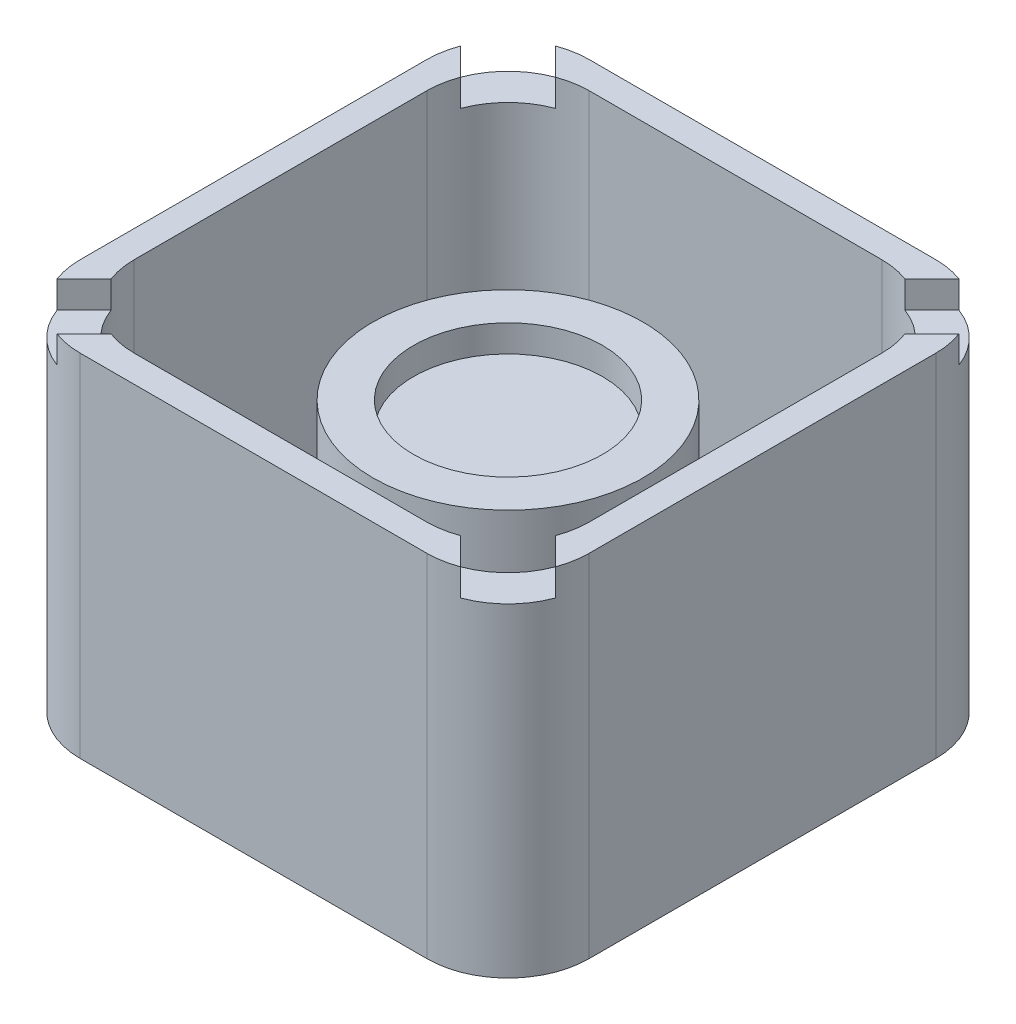
SolidWorks part; units mm, degrees
ref_plane "前视基准面" through (0, 0, 0) normal (0, 0, 1) x (1, 0, 0)
ref_plane "上视基准面" through (0, 0, 0) normal (0, 1, 0) x (1, 0, 0)
ref_plane "右视基准面" through (0, 0, 0) normal (1, 0, 0) x (0, 0, -1)
sketch "草图1" plane through (0, 0, 0) normal (0, 1, 0) x (1, 0, 0)
  line L0 (8.5413, 10.2987) -> (6.4721, 8.2295)
  line L1 (-6.42, 9.42) -> (6.42, 9.42)
  line L2 (-9.42, 6.42) -> (-9.42, -6.42)
  line L3 (-6.42, -9.42) -> (6.42, -9.42)
  line L4 (9.42, 6.42) -> (9.42, -6.42)
  line L5 (0, -9.42) -> (0, 9.42) construction
  line L6 (-9.42, 0) -> (9.42, 0) construction
  line L7 (-9.42, 9.42) -> (9.42, 9.42)
  line L8 (-9.42, 9.42) -> (-9.42, 28.26)
  line L9 (-9.42, 28.26) -> (9.42, 28.26)
  line L10 (9.42, 9.42) -> (9.42, 28.26)
  line L11 (0, 28.26) -> (0, 9.42) construction
  line L12 (-9.42, 18.84) -> (9.42, 18.84) construction
  line L13 (6.42, 12.42) -> (8.5413, 10.2987)
  line L14 (-5.42, 8.42) -> (5.42, 8.42)
  line L15 (8.42, 5.42) -> (8.42, -5.42)
  line L16 (-5.42, -8.42) -> (5.42, -8.42)
  line L17 (-8.42, 5.42) -> (-8.42, -5.42)
  line L18 (-9.42, 8.42) -> (9.42, 8.42) construction
  line L19 (-8.42, 9.42) -> (-8.42, -8.42) construction
  line L20 (8.42, 9.42) -> (8.42, -8.42) construction
  line L21 (-9.42, 9.42) -> (9.42, 9.42) construction
  line L22 (-9.42, 9.42) -> (-9.42, -9.42) construction
  line L23 (-9.42, -9.42) -> (9.42, -9.42) construction
  line L24 (-8.42, -8.42) -> (8.42, -8.42) construction
  line L25 (9.42, 9.42) -> (9.42, -9.42) construction
  line L26 (0, 0) -> (6.42, 6.42)
  line L27 (10.2987, 8.5413) -> (8.2295, 6.4721)
  line L28 (10.2987, -8.5413) -> (8.2295, -6.4721)
  line L29 (8.5413, -10.2987) -> (6.4721, -8.2295)
  line L30 (-8.5413, -10.2987) -> (-6.4721, -8.2295)
  line L31 (-10.2987, -8.5413) -> (-8.2295, -6.4721)
  line L32 (-10.2987, 8.5413) -> (-8.2295, 6.4721)
  line L33 (-8.5413, 10.2987) -> (-6.4721, 8.2295)
  circle A0 centre (6.42, 12.42) radius 3
  arc A1 (-6.42, 9.42) -> (-9.42, 6.42) centre (-6.42, 6.42) ccw
  arc A2 (-5.42, 8.42) -> (-8.42, 5.42) centre (-5.42, 5.42) ccw
  arc A3 (-6.42, -9.42) -> (-9.42, -6.42) centre (-6.42, -6.42) cw
  arc A4 (-5.42, -8.42) -> (-8.42, -5.42) centre (-5.42, -5.42) cw
  arc A5 (5.42, -8.42) -> (8.42, -5.42) centre (5.42, -5.42) ccw
  arc A6 (6.42, -9.42) -> (9.42, -6.42) centre (6.42, -6.42) ccw
  arc A7 (8.42, 5.42) -> (5.42, 8.42) centre (5.42, 5.42) ccw
  arc A8 (9.42, 6.42) -> (6.42, 9.42) centre (6.42, 6.42) ccw
  point P0 (0, 0)
  point P65 (0, 0)
  point P240 (0, 18.84)
  dimension "D4" = 6
  dimension "D6" = 3
  dimension "D1" = 16.84
  dimension "D2" = 18.84
  dimension "D3" = 18.84
  dimension "D5" = 1
  dimension "D7" = 16.84
  dimension "D8" = 4
extrude "凸台-拉伸3" add sketch "草图1" against normal blind 10 contours L31 A4 L17 A2 L32 A1 L2 A3 | A2 L33 A1 L32 | L0 A8 L1 A1 L33 A2 L14 A7 | L30 A4 L31 A3 | L3 A6 L29 A5 L16 A4 L30 A3 | L29 A6 L28 A5 | L4 A8 L27 A7 L15 A5 L28 A6 | L27 A8 L0 A7 region at (0, 0, -8.9199) region at (7.979, 0, -7.979) region at (8.9199, 0, 0) region at (-7.979, 0, -7.979) region at (-8.9199, 0, 0) region at (7.979, 0, 7.979) region at (0, 0, 8.9199) region at (-7.979, 0, 7.979)
extrude "凸台-拉伸4" add sketch "草图1<6>" against normal blind 2 from surface contours L15 A7 L14 A2 L17 A4 L16 A5 | A2 L33 A1 L32 | L31 A4 L17 A2 L32 A1 L2 A3 | L30 A4 L31 A3 | L3 A6 L29 A5 L16 A4 L30 A3 | L4 A8 L27 A7 L15 A5 L28 A6 | L29 A6 L28 A5 | L0 A8 L1 A1 L33 A2 L14 A7 | L27 A8 L0 A7 region at (0, 0, -8.9199) region at (7.979, 0, -7.979) region at (7.3729, 0, -7.3729) region at (8.9199, 0, 0) region at (-7.979, 0, -7.979) region at (-8.9199, 0, 0) region at (7.979, 0, 7.979) region at (0, 0, 8.9199) region at (-7.979, 0, 7.979) starting at face at (0, -10, 0)
sketch "草图1<6>" plane through (0, 0, 0) normal (0, 1, 0) x (1, 0, 0) same geometry as "草图1"
extrude "凸台-拉伸5" add sketch "草图1<7>" along normal blind 1 contours L31 A4 L17 A2 L32 A1 L2 A3 | L0 A8 L1 A1 L33 A2 L14 A7 | L4 A8 L27 A7 L15 A5 L28 A6 | L3 A6 L29 A5 L16 A4 L30 A3 region at (0, 0, -8.9199) region at (8.9199, 0, 0) region at (-8.9199, 0, 0) region at (0, 0, 8.9199)
sketch "草图1<7>" plane through (0, 0, 0) normal (0, 1, 0) x (1, 0, 0) same geometry as "草图1"
sketch "草图2" plane through (0, -10, 0) normal (0, 1, 0) x (1, 0, 0)
  circle A0 centre (0, 0) radius 5
  circle A1 centre (0, 0) radius 3.5
extrude "凸台-拉伸6" add sketch "草图2" along normal blind 8
extrude "凸台-拉伸7" add sketch "草图2<2>" along normal blind 7 contours A1 region at (0, -10, 0)
sketch "草图2<2>" plane through (0, -10, 0) normal (0, 1, 0) x (1, 0, 0) same geometry as "草图2"
